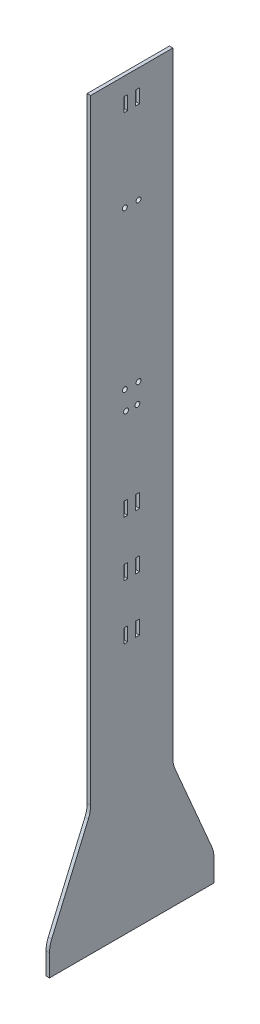
SolidWorks part; units mm, degrees
ref_plane "Front Plane" through (0, 0, 0) normal (0, 0, 1) x (1, 0, 0)
ref_plane "Top Plane" through (0, 0, 0) normal (0, 1, 0) x (1, 0, 0)
ref_plane "Right Plane" through (0, 0, 0) normal (1, 0, 0) x (0, 0, -1)
sketch "Sketch1" plane through (0, 0, 0) normal (1, 0, 0) x (0, 0, -1)
  line L1 (-38.1, 457.2) -> (38.1, 457.2)
  line L2 (-38.1, 457.2) -> (-38.1, -457.2)
  line L3 (-38.1, -457.2) -> (38.1, -457.2)
  line L4 (38.1, 457.2) -> (38.1, -457.2)
  line L5 (-38.1, 457.2) -> (38.1, -457.2) construction
  line L6 (-38.1, -457.2) -> (38.1, 457.2) construction
  point P0 (0, 0)
  dimension "D1" = 914.4
  dimension "D2" = 76.2
extrude "Boss-Extrude1" add sketch "Sketch1" along normal blind 3.175
sketch "Sketch2" plane through (3.175, 0, 0) normal (1, 0, 0) x (0, 0, -1)
  line L0 (-38.1, -457.2) -> (38.1, -457.2) construction
  line L1 (3.722, -204.5335) -> (7.278, -204.5335)
  line L2 (3.722, -204.5335) -> (3.722, -217.4875)
  line L3 (3.722, -217.4875) -> (7.278, -217.4875)
  line L4 (7.278, -204.5335) -> (7.278, -217.4875)
  line L5 (3.722, -204.5335) -> (7.278, -217.4875) construction
  line L6 (3.722, -217.4875) -> (7.278, -204.5335) construction
  point P0 (5.5, -211.0105)
  dimension "D1" = 3.556
  dimension "D2" = 12.954
  dimension "D3" = 239.7125
  dimension "D4" = 3.722
extrude "Cut-Extrude1" cut sketch "Sketch2" against normal through all
mirror "Mirror1" about plane through (0, 0, 0) normal (0, 0, 1) of "Cut-Extrude1"
pattern_linear "LPattern1" count 2 spacing 50.8 along (0, 1, 0) count 2 spacing 50.8 along (0, -1, 0) of "Mirror1"
sketch "Sketch3" plane through (3.175, 0, 0) normal (1, 0, 0) x (0, 0, -1)
  line L0 (7.278, -153.7335) -> (3.722, -153.7335) construction
  line L1 (3.722, 170.9081) -> (7.278, 170.9081)
  line L2 (3.722, 170.9081) -> (3.722, 157.9541)
  line L3 (3.722, 157.9541) -> (7.278, 157.9541)
  line L4 (7.278, 170.9081) -> (7.278, 157.9541)
  line L5 (3.722, 170.9081) -> (7.278, 157.9541) construction
  line L6 (3.722, 157.9541) -> (7.278, 170.9081) construction
  line L7 (7.278, -166.6875) -> (7.278, -153.7335) construction
  line L9 (0, 0) -> (0, 53.0447) construction
  line L10 (-3.722, 157.9541) -> (-7.278, 170.9081) construction
  line L11 (-3.722, 170.9081) -> (-7.278, 157.9541) construction
  line L12 (-7.278, 170.9081) -> (-7.278, 157.9541)
  line L13 (-3.722, 157.9541) -> (-7.278, 157.9541)
  line L14 (-3.722, 170.9081) -> (-3.722, 157.9541)
  line L15 (-3.722, 170.9081) -> (-7.278, 170.9081)
  point P0 (5.5, 164.4311)
  point P19 (-5.5, 164.4311)
extrude "Cut-Extrude2" cut sketch "Sketch3" against normal through all
hole_wizard "#8 Clearance Hole1" positions "Sketch4" profile "Sketch5" hole size "#8" standard "ANSI Inch" end condition through all
sketch "Sketch4" plane through (3.175, 0, 0) normal (1, 0, 0) x (0, 0, -1)
  point P0 (6.35, -64.5237)
  point P3 (-6.35, -64.5237)
  point P6 (6.35, 81.272)
  point P9 (-6.35, 81.272)
  point P12 (5.25, -82.2261)
  point P15 (-5.25, -82.2261)
sketch "Sketch5" plane through (3.175, -64.5237, -6.35) normal (0, 1, 0) x (0, 0, -1)
  line L0 (0, 0) -> (0, 3.175)
  line L1 (0, 3.175) -> (2.2479, 3.175)
  line L2 (2.2479, 3.175) -> (2.2479, 0)
  line L5 (2.2479, 0) -> (0, 0)
  line L11 (0, -6.35) -> (0, 107.95) construction
  dimension "Thru Hole Dia." = 4.4958
  dimension "Thru Hole Depth" = 3.175
sketch "Sketch6" plane through (3.175, 0, 0) normal (1, 0, 0) x (0, 0, -1)
  line L0 (0, -457.2) -> (0, 187.325) construction
  line L1 (-38.1, -457.2) -> (38.1, -457.2) construction
  line L2 (-38.1, 187.325) -> (38.1, 187.325)
  line L4 (-38.1, 457.2) -> (-38.1, -457.2) construction
  line L5 (38.1, -457.2) -> (38.1, 457.2) construction
  dimension "D1" = 644.525
extrude "Cut-Extrude3" cut sketch "Sketch6" against normal through all and the other way through all
sketch "Sketch7" plane through (3.175, 0, 0) normal (1, 0, 0) x (0, 0, -1)
  line L0 (0, -457.2) -> (0, -501.65) construction
  line L1 (-38.1, -457.2) -> (38.1, -457.2) construction
  line L2 (-38.1, -457.2) -> (-38.1, -501.65)
  line L3 (-38.1, -501.65) -> (0, -501.65)
  line L4 (38.1, -457.2) -> (38.1, -501.65)
  line L5 (38.1, -501.65) -> (0, -501.65)
  line L6 (-38.1, -457.2) -> (38.1, -457.2)
  dimension "D1" = 44.45
extrude "Boss-Extrude2" add sketch "Sketch7" against normal up to surface (3.175 mm away) up to face at (0, -160.2105, 5.5)
sketch "Sketch8" plane through (3.175, 0, 0) normal (1, 0, 0) x (0, 0, -1)
  line L0 (-38.1, -387.35) -> (-76.2, -476.25)
  line L1 (-38.1, 187.325) -> (-38.1, -501.65) construction
  line L2 (-76.2, -476.25) -> (-76.2, -501.65)
  line L3 (-76.2, -501.65) -> (76.2, -501.65)
  line L4 (76.2, -501.65) -> (76.2, -476.25)
  line L5 (76.2, -476.25) -> (38.1, -387.35)
  line L6 (38.1, -501.65) -> (38.1, 187.325) construction
  line L7 (-38.1, -501.65) -> (38.1, -501.65) construction
  line L8 (-38.1, -387.35) -> (38.1, -387.35)
  dimension "D1" = 152.4
  dimension "D2" = 38.1
  dimension "D3" = 25.4
  dimension "D4" = 114.3
extrude "Boss-Extrude3" add sketch "Sketch8" against normal blind 3.175
fillet "Fillet1" radius 25.4 4 edges at (1.5875, -476.25, -76.2) (1.5875, -476.25, 76.2) (1.5875, -387.35, 38.1) (1.5875, -387.35, -38.1)
